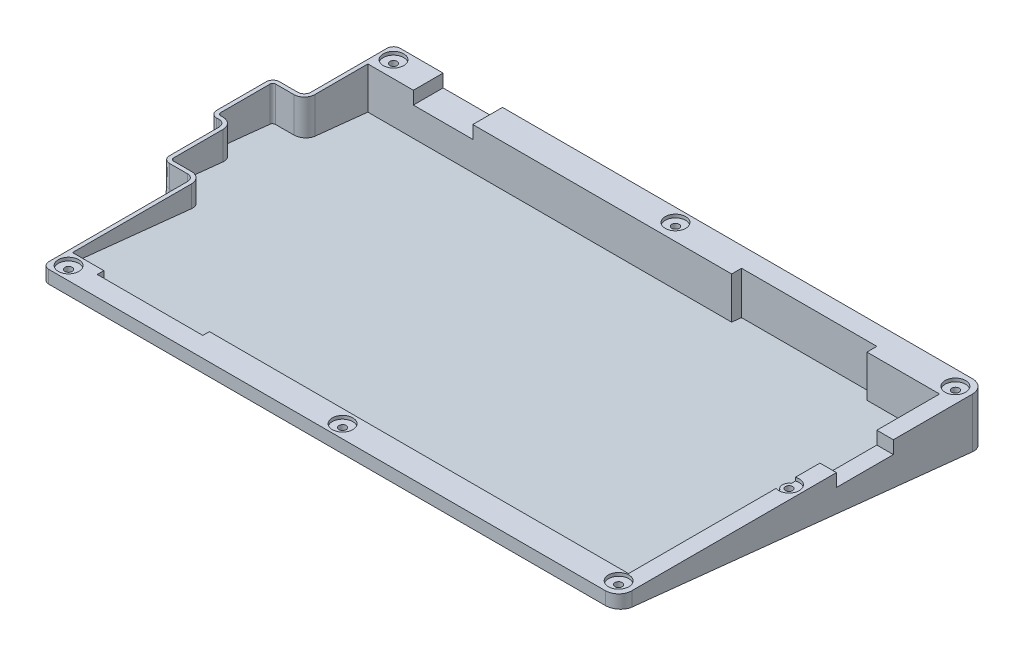
SolidWorks part; units mm, degrees
ref_plane "Front Plane" through (0, 0, 0) normal (0, 0, 1) x (1, 0, 0)
ref_plane "Top Plane" through (0, 0, 0) normal (0, 1, 0) x (1, 0, 0)
ref_plane "Right Plane" through (0, 0, 0) normal (1, 0, 0) x (0, 0, -1)
sketch "Sketch1" plane through (0, 0, 0) normal (0, 1, 0) x (1, 0, 0)
  line L0 (138.4196, 31.7518) -> (125.4196, 31.7518)
  line L1 (-35.0204, 31.7518) -> (107.4196, 31.7518)
  line L2 (140.4196, 29.7518) -> (140.4196, 6.7018)
  line L3 (-34.0204, 3.7518) -> (-34.0204, 22.7518)
  line L4 (136.4596, 27.7518) -> (136.4396, 27.7518)
  line L5 (142.4196, 4.7018) -> (147.9496, 4.7018)
  line L6 (-34.0204, 22.7518) -> (-12.0204, 22.7518)
  line L8 (149.9496, 2.7018) -> (149.9496, -12.3482)
  line L11 (147.9496, -14.3482) -> (147.1896, -14.3482)
  line L14 (145.1896, -16.3482) -> (145.1896, -31.3982)
  line L17 (143.1896, -33.3982) -> (137.6696, -33.3982)
  line L20 (135.6696, -35.3982) -> (135.6696, -77.4982)
  line L21 (-34.0204, -25.6003) -> (-34.0204, -71.4982)
  line L23 (133.6696, -79.4982) -> (-35.0204, -79.4982)
  line L28 (-39.0204, 27.7518) -> (-39.0204, 3.7518)
  line L31 (-34.0204, 3.7518) -> (-39.0204, 3.7518)
  line L32 (-34.0204, -13.4982) -> (-39.0204, -13.4982)
  line L33 (-39.0204, -75.4982) -> (-39.0204, -13.4982)
  line L34 (-34.0204, -71.4982) -> (92.9796, -71.4982)
  line L35 (92.9796, -71.4982) -> (92.9796, -73.4982)
  line L36 (92.9796, -73.4982) -> (124.9796, -73.4982)
  line L37 (124.9796, -73.4982) -> (124.9796, -71.4982)
  line L39 (134.4706, -35.3982) -> (134.4706, -71.4982)
  line L40 (134.4706, -71.4982) -> (124.9796, -71.4982)
  line L41 (137.6696, -32.1992) -> (143.1896, -32.1992)
  line L42 (-34.0204, -13.4982) -> (-34.0204, -22.1362)
  line L43 (143.9906, -31.3982) -> (143.9906, -16.3482)
  line L44 (-12.0204, 22.7518) -> (-12.0204, 25.7518)
  line L45 (147.1896, -13.1492) -> (147.9496, -13.1492)
  line L46 (148.7506, -12.3482) -> (148.7506, 2.7018)
  line L47 (-12.0204, 25.7518) -> (28.9796, 25.7518)
  line L48 (28.9796, 25.7518) -> (28.9796, 22.7518)
  line L49 (28.9796, 22.7518) -> (107.4196, 22.7518)
  line L50 (147.9496, 3.5027) -> (142.4196, 3.5027)
  line L51 (107.4196, 22.7518) -> (107.4196, 31.7518)
  line L52 (139.2206, 6.7018) -> (139.2206, 22.7518)
  line L53 (125.4196, 31.7518) -> (125.4196, 22.7518)
  line L54 (139.2206, 22.7518) -> (125.4196, 22.7518)
  arc A0 (138.4196, 31.7518) -> (140.4196, 29.7518) centre (138.4196, 29.7518) cw
  arc A1 (140.4196, 6.7018) -> (142.4196, 4.7018) centre (142.4196, 6.7018) ccw
  arc A2 (149.9496, 2.7018) -> (147.9496, 4.7018) centre (147.9496, 2.7018) ccw
  arc A3 (149.9496, -12.3482) -> (147.9496, -14.3482) centre (147.9496, -12.3482) cw
  arc A4 (147.1896, -14.3482) -> (145.1896, -16.3482) centre (147.1896, -16.3482) ccw
  arc A5 (145.1896, -31.3982) -> (143.1896, -33.3982) centre (143.1896, -31.3982) cw
  arc A6 (-35.0204, 31.7518) -> (-39.0204, 27.7518) centre (-35.0204, 27.7518) ccw
  arc A7 (-39.0204, -75.4982) -> (-35.0204, -79.4982) centre (-35.0204, -75.4982) ccw
  arc A8 (133.6696, -79.4982) -> (135.6696, -77.4982) centre (133.6696, -77.4982) ccw
  arc A9 (135.6696, -35.3982) -> (137.6696, -33.3982) centre (137.6696, -35.3982) cw
  circle A10 centre (-34.4204, 27.1518) radius 1.1
  circle A11 centre (51.0096, 27.7518) radius 1.1
  circle A12 centre (136.4396, 27.7518) radius 1.1
  circle A13 centre (-34.4204, -74.8982) radius 1.1
  circle A14 centre (48.6296, -75.4982) radius 1.1
  circle A15 centre (131.6496, -75.4982) radius 1.1
  circle A16 centre (-35.0204, -23.8682) radius 1.1
  arc A27 (-34.0204, -22.1362) -> (-34.0204, -25.6003) centre (-35.0204, -23.8682) cw
  arc A28 (139.2206, 6.7018) -> (142.4196, 3.5027) centre (142.4196, 6.7018) ccw
  arc A29 (147.9496, 3.5027) -> (148.7506, 2.7018) centre (147.9496, 2.7018) cw
  arc A30 (148.7506, -12.3482) -> (147.9496, -13.1492) centre (147.9496, -12.3482) cw
  arc A31 (147.1896, -13.1492) -> (143.9906, -16.3482) centre (147.1896, -16.3482) ccw
  arc A32 (143.9906, -31.3982) -> (143.1896, -32.1992) centre (143.1896, -31.3982) cw
  arc A33 (137.6696, -32.1992) -> (134.4706, -35.3982) centre (137.6696, -35.3982) ccw
extrude "Boss-Extrude2" add sketch "Sketch1" against normal blind 4.7 contours L41 A33 L39 L40 L37 L36 L35 L34 L21 A27 L42 L32 L33 A7 L23 A8 L20 A9 L17 A5 L14 A4 L11 A3 L8 A2 L5 A1 L2 A0 L0 L53 L54 L52 A28 L50 A29 L46 A30 L45 A31 L43 A32 A12 A13 A14 A15 | L1 A6 L28 L31 L3 L6 L44 L47 L48 L49 L51 A11 A10 region at (138.2833, 0, -29.6154) region at (31.7683, 0, -26.4895)
move or copy body "Body-Move/Copy1" bodies to move or copy 105 104 copy no rotation origin (55.4646, -2.35, 0) rotation axis (0, 0, 1) rotation angle 180
sketch "Sketch3" plane through (149.9496, 0, 0) normal (1, 0, 0) x (0, 0, -1)
  line L0 (-79.4982, 0) -> (-79.4982, -4.7) construction
  line L1 (-79.4982, 0) -> (-79.4982, -4.7)
  line L2 (31.7518, 0) -> (31.7518, -4.7) construction
  line L3 (31.7518, 0) -> (31.7518, -4.7)
  line L5 (-79.4982, -4.7) -> (31.7518, -16.3928)
  line L6 (31.7518, -16.3928) -> (31.7518, -4.7)
  line L7 (31.7518, -4.7) -> (-79.4982, -4.7)
  line M3 (-75.4982, -4.7) -> (-13.4982, -4.7)
  dimension "D1" = 6
extrude "Boss-Extrude3" add sketch "Sketch3" against normal up to surface (188.97 mm away) contours L6 L7 L5 M3 region at (149.9496, -8.5976, 5.3315) up to face at (-39.0204, -2.35, 4.8232)
sketch "Sketch4" plane through (0, -4.7, 0) normal (0, 1, 0) x (1, 0, 0)
  line L2 (145.9496, -79.4982) -> (149.9496, -79.4982)
  line L3 (149.9496, -79.4982) -> (149.9496, -75.4982)
  line L4 (-29.4904, 6.7018) -> (-29.4904, 29.7518)
  line L5 (-27.4904, 31.7518) -> (-39.0204, 31.7518)
  line L6 (-36.2604, -14.3482) -> (-37.0204, -14.3482)
  line L7 (-39.0204, -12.3482) -> (-39.0204, -79.4982)
  line L8 (-39.0204, -79.4982) -> (-22.7404, -79.4982)
  line L9 (-24.7404, -77.4982) -> (-24.7404, -35.3982)
  line L10 (-26.7404, -33.3982) -> (-32.2604, -33.3982)
  line L11 (-34.2604, -31.3982) -> (-34.2604, -16.3482)
  line L12 (-36.2604, -14.3482) -> (-37.0204, -14.3482)
  line L13 (-39.0204, -12.3482) -> (-39.0204, -79.4982)
  line L14 (-39.0204, -79.4982) -> (-22.7404, -79.4982)
  line L15 (-24.7404, -77.4982) -> (-24.7404, -35.3982)
  line L16 (-26.7404, -33.3982) -> (-32.2604, -33.3982)
  line L17 (-34.2604, -31.3982) -> (-34.2604, -16.3482)
  line L18 (-39.0204, 31.7518) -> (-39.0204, 2.7018)
  line L19 (-37.0204, 4.7018) -> (-31.4904, 4.7018)
  line L20 (-29.4904, 6.7018) -> (-29.4904, 29.7518)
  line L21 (-27.4904, 31.7518) -> (-39.0204, 31.7518)
  line L22 (-39.0204, 31.7518) -> (-39.0204, 2.7018)
  line L23 (-37.0204, 4.7018) -> (-31.4904, 4.7018)
  line L24 (145.9496, -79.4982) -> (149.9496, -79.4982)
  line L25 (149.9496, -79.4982) -> (149.9496, -75.4982)
  line L26 (149.9496, 31.7518) -> (145.9496, 31.7518)
  line L27 (149.9496, 27.7518) -> (149.9496, 31.7518)
  line L28 (149.9496, 31.7518) -> (145.9496, 31.7518)
  line L29 (149.9496, 27.7518) -> (149.9496, 31.7518)
  arc A1 (145.9496, -79.4982) -> (149.9496, -75.4982) centre (145.9496, -75.4982) ccw
  arc A2 (145.9496, -79.4982) -> (149.9496, -75.4982) centre (145.9496, -75.4982) ccw
  arc A3 (-27.4904, 31.7518) -> (-29.4904, 29.7518) centre (-27.4904, 29.7518) ccw
  arc A4 (-37.0204, 4.7018) -> (-39.0204, 2.7018) centre (-37.0204, 2.7018) ccw
  arc A5 (-39.0204, -12.3482) -> (-37.0204, -14.3482) centre (-37.0204, -12.3482) ccw
  arc A6 (-24.7404, -77.4982) -> (-22.7404, -79.4982) centre (-22.7404, -77.4982) ccw
  arc A7 (-24.7404, -35.3982) -> (-26.7404, -33.3982) centre (-26.7404, -35.3982) ccw
  arc A8 (-34.2604, -31.3982) -> (-32.2604, -33.3982) centre (-32.2604, -31.3982) ccw
  arc A9 (-34.2604, -16.3482) -> (-36.2604, -14.3482) centre (-36.2604, -16.3482) ccw
  arc A10 (-39.0204, -12.3482) -> (-37.0204, -14.3482) centre (-37.0204, -12.3482) ccw
  arc A11 (-24.7404, -77.4982) -> (-22.7404, -79.4982) centre (-22.7404, -77.4982) ccw
  arc A12 (-24.7404, -35.3982) -> (-26.7404, -33.3982) centre (-26.7404, -35.3982) ccw
  arc A13 (-34.2604, -31.3982) -> (-32.2604, -33.3982) centre (-32.2604, -31.3982) ccw
  arc A14 (-34.2604, -16.3482) -> (-36.2604, -14.3482) centre (-36.2604, -16.3482) ccw
  arc A15 (-31.4904, 4.7018) -> (-29.4904, 6.7018) centre (-31.4904, 6.7018) ccw
  arc A16 (-27.4904, 31.7518) -> (-29.4904, 29.7518) centre (-27.4904, 29.7518) ccw
  arc A17 (-37.0204, 4.7018) -> (-39.0204, 2.7018) centre (-37.0204, 2.7018) ccw
  arc A18 (-31.4904, 4.7018) -> (-29.4904, 6.7018) centre (-31.4904, 6.7018) ccw
  arc A19 (149.9496, 27.7518) -> (145.9496, 31.7518) centre (145.9496, 27.7518) ccw
  arc A20 (149.9496, 27.7518) -> (145.9496, 31.7518) centre (145.9496, 27.7518) ccw
  dimension "D1" = 0
  dimension "D2" = 0
  dimension "D3" = 0
  dimension "D4" = 0
extrude "Cut-Extrude1" cut sketch "Sketch4" against normal through all
ref_plane "Plane4" through (0, 15, 0) normal (0, 1, 0) x (1, 0, 0)
sketch "Sketch10" plane through (0, 15, 0) normal (0, 1, 0) x (1, 0, 0)
  line L0 (-14.4904, 22.7518) -> (3.5096, 22.7518)
  line L1 (144.9496, 3.7518) -> (144.9496, -13.4982)
  line L27 (-14.4904, 31.7518) -> (-14.4904, 22.7518)
  line L28 (-14.4904, 22.7518) -> (-28.2913, 22.7518)
  line L29 (-28.2913, 22.7518) -> (-28.2913, 6.7018)
  line L30 (-31.4904, 3.5027) -> (-37.0204, 3.5027)
  line L31 (-37.8213, 2.7018) -> (-37.8213, -12.3482)
  line L32 (-37.0204, -13.1492) -> (-36.2604, -13.1492)
  line L33 (-33.0613, -16.3482) -> (-33.0613, -31.3982)
  line L34 (-32.2604, -32.1992) -> (-26.7404, -32.1992)
  line L35 (-23.5413, -35.3982) -> (-23.5413, -71.4982)
  line L36 (-23.5413, -71.4982) -> (-14.0504, -71.4982)
  line L37 (-14.0504, -71.4982) -> (-14.0504, -73.4982)
  line L38 (-14.0504, -73.4982) -> (17.9496, -73.4982)
  line L39 (17.9496, -73.4982) -> (17.9496, -71.4982)
  line L40 (17.9496, -71.4982) -> (144.9496, -71.4982)
  line L41 (144.9496, -71.4982) -> (144.9496, -25.6003)
  line L42 (144.9496, -22.1362) -> (144.9496, -13.4982)
  line L43 (144.9496, -13.4982) -> (149.9496, -13.4982)
  line L44 (149.9496, -13.4982) -> (149.9496, 3.7518)
  line L45 (149.9496, 3.7518) -> (144.9496, 3.7518)
  line L46 (144.9496, 3.7518) -> (144.9496, 22.7518)
  line L47 (144.9496, 22.7518) -> (122.9496, 22.7518)
  line L48 (122.9496, 22.7518) -> (122.9496, 25.7518)
  line L49 (122.9496, 25.7518) -> (81.9496, 25.7518)
  line L50 (81.9496, 25.7518) -> (81.9496, 22.7518)
  line L51 (81.9496, 22.7518) -> (3.5096, 22.7518)
  line L52 (3.5096, 22.7518) -> (3.5096, 31.7518)
  line L53 (3.5096, 31.7518) -> (-14.4904, 31.7518)
  line L54 (-14.4904, 31.7518) -> (-14.4904, 22.7518)
  line L55 (-14.4904, 22.7518) -> (-28.2913, 22.7518)
  line L56 (-28.2913, 22.7518) -> (-28.2913, 6.7018)
  line L57 (-31.4904, 3.5027) -> (-37.0204, 3.5027)
  line L58 (-37.8213, 2.7018) -> (-37.8213, -12.3482)
  line L59 (-37.0204, -13.1492) -> (-36.2604, -13.1492)
  line L60 (-33.0613, -16.3482) -> (-33.0613, -31.3982)
  line L61 (-32.2604, -32.1992) -> (-26.7404, -32.1992)
  line L62 (-23.5413, -35.3982) -> (-23.5413, -71.4982)
  line L63 (-23.5413, -71.4982) -> (-14.0504, -71.4982)
  line L64 (-14.0504, -71.4982) -> (-14.0504, -73.4982)
  line L65 (-14.0504, -73.4982) -> (17.9496, -73.4982)
  line L66 (17.9496, -73.4982) -> (17.9496, -71.4982)
  line L67 (17.9496, -71.4982) -> (144.9496, -71.4982)
  line L68 (144.9496, -71.4982) -> (144.9496, -25.6003)
  line L69 (144.9496, -22.1362) -> (144.9496, -13.4982)
  line L70 (144.9496, -13.4982) -> (149.9496, -13.4982)
  line L71 (149.9496, -13.4982) -> (149.9496, 3.7518)
  line L72 (149.9496, 3.7518) -> (144.9496, 3.7518)
  line L73 (144.9496, 3.7518) -> (144.9496, 22.7518)
  line L74 (144.9496, 22.7518) -> (122.9496, 22.7518)
  line L75 (122.9496, 22.7518) -> (122.9496, 25.7518)
  line L76 (122.9496, 25.7518) -> (81.9496, 25.7518)
  line L77 (81.9496, 25.7518) -> (81.9496, 22.7518)
  line L78 (81.9496, 22.7518) -> (3.5096, 22.7518)
  line L79 (3.5096, 22.7518) -> (3.5096, 31.7518)
  line L80 (3.5096, 31.7518) -> (-14.4904, 31.7518)
  arc A7 (-31.4904, 3.5027) -> (-28.2913, 6.7018) centre (-31.4904, 6.7018) ccw
  arc A8 (-37.0204, 3.5027) -> (-37.8213, 2.7018) centre (-37.0204, 2.7018) ccw
  arc A9 (-37.8213, -12.3482) -> (-37.0204, -13.1492) centre (-37.0204, -12.3482) ccw
  arc A10 (-33.0613, -16.3482) -> (-36.2604, -13.1492) centre (-36.2604, -16.3482) ccw
  arc A11 (-33.0613, -31.3982) -> (-32.2604, -32.1992) centre (-32.2604, -31.3982) ccw
  arc A12 (-23.5413, -35.3982) -> (-26.7404, -32.1992) centre (-26.7404, -35.3982) ccw
  arc A13 (144.9496, -22.1362) -> (144.9496, -25.6003) centre (145.9496, -23.8682) ccw
  arc A14 (-31.4904, 3.5027) -> (-28.2913, 6.7018) centre (-31.4904, 6.7018) ccw
  arc A15 (-37.0204, 3.5027) -> (-37.8213, 2.7018) centre (-37.0204, 2.7018) ccw
  arc A16 (-37.8213, -12.3482) -> (-37.0204, -13.1492) centre (-37.0204, -12.3482) ccw
  arc A17 (-33.0613, -16.3482) -> (-36.2604, -13.1492) centre (-36.2604, -16.3482) ccw
  arc A18 (-33.0613, -31.3982) -> (-32.2604, -32.1992) centre (-32.2604, -31.3982) ccw
  arc A19 (-23.5413, -35.3982) -> (-26.7404, -32.1992) centre (-26.7404, -35.3982) ccw
  arc A20 (144.9496, -22.1362) -> (144.9496, -25.6003) centre (145.9496, -23.8682) ccw
  dimension "D1" = 0
extrude "Cut-Extrude2" cut sketch "Sketch10" against normal through all contours A20 L69 L1 L73 L74 L75 L76 L77 L78 L0 L55 L56 A14 L57 A15 L58 A16 L59 A17 L60 A18 L61 A19 L62 L63 L64 L65 L66 L67 L68 region at (57.9798, 15, 23.6888)
sketch "Sketch11" plane through (144.9496, 0, 0) normal (-1, 0, 0) x (0, 0, 1)
  line L0 (-22.7518, -15.4469) -> (71.4982, -5.5408)
  line L1 (71.4982, -5.5408) -> (71.4982, -3.5408)
  line L2 (71.4982, 0) -> (71.4982, -5.5408) construction
  line L3 (71.4982, -3.5408) -> (-22.7518, -13.4469)
  line L4 (-22.7518, 0) -> (-22.7518, -15.4469) construction
  line L5 (-22.7518, -13.4469) -> (-22.7518, -15.4469)
  dimension "D1" = 2
  dimension "D2" = 2
extrude "Boss-Extrude4" add sketch "Sketch11" along normal up to surface (182.7709 mm away)
sketch "Sketch12" plane through (0, -10.9348, 1.1493) normal (0, 0.9945, -0.1045) x (1, 0, 0)
  line L0 (-29.4904, 7.8943) -> (-29.4904, 24.0327) construction
  line L1 (-29.4904, 24.0327) -> (-37.8213, 24.0327) construction
  line L2 (-37.8213, 24.0327) -> (-37.8213, 5.715) construction
  line L3 (-37.0204, 5.8833) -> (-31.4904, 5.8833) construction
  line L4 (-36.2604, -13.2716) -> (-37.0204, -13.2716) construction
  line L5 (-37.8213, -13.1033) -> (-37.8213, -70.7364) construction
  line L6 (-37.8213, -70.7364) -> (-24.7404, -70.7364) construction
  line L7 (-24.7404, -70.7364) -> (-24.7404, -34.4376) construction
  line L8 (-26.7404, -32.4266) -> (-32.2604, -32.4266) construction
  line L9 (-34.2604, -30.4155) -> (-34.2604, -15.2826) construction
  line L10 (-29.4904, 7.8943) -> (-29.4904, 24.0327)
  line L11 (-29.4904, 24.0327) -> (-37.8213, 24.0327)
  line L12 (-37.8213, 24.0327) -> (-37.8213, 5.715)
  line L13 (-37.0204, 5.8833) -> (-31.4904, 5.8833)
  line L14 (-36.2604, -13.2716) -> (-37.0204, -13.2716)
  line L15 (-37.8213, -13.1033) -> (-37.8213, -70.7364)
  line L16 (-37.8213, -70.7364) -> (-24.7404, -70.7364)
  line L17 (-24.7404, -70.7364) -> (-24.7404, -34.4376)
  line L18 (-26.7404, -32.4266) -> (-32.2604, -32.4266)
  line L19 (-34.2604, -30.4155) -> (-34.2604, -15.2826)
  line L20 (-37.8213, 24.0327) -> (-37.8213, 25.9101)
  line L21 (-29.4904, 24.0327) -> (-29.4904, 27.1127)
  line L22 (-29.4904, 27.1127) -> (-37.8213, 25.9101)
  ellipse E0 centre (-31.4904, 7.8943) end of major axis (-31.4904, 9.9053) minor radius 2 (-31.4904, 5.8833) -> (-29.4904, 7.8943) ccw construction
  ellipse E1 centre (-37.0204, 3.8723) end of major axis (-37.0204, 5.8833) minor radius 2 (-37.0204, 5.8833) -> (-37.8213, 5.715) ccw construction
  ellipse E2 centre (-37.0204, -11.2606) end of major axis (-37.0204, -9.2496) minor radius 2 (-37.8213, -13.1033) -> (-37.0204, -13.2716) ccw construction
  ellipse E3 centre (-26.7404, -34.4376) end of major axis (-26.7404, -32.4266) minor radius 2 (-24.7404, -34.4376) -> (-26.7404, -32.4266) ccw construction
  ellipse E4 centre (-32.2604, -30.4155) end of major axis (-32.2604, -28.4045) minor radius 2 (-34.2604, -30.4155) -> (-32.2604, -32.4266) ccw construction
  ellipse E5 centre (-36.2604, -15.2826) end of major axis (-36.2604, -13.2716) minor radius 2 (-34.2604, -15.2826) -> (-36.2604, -13.2716) ccw construction
  ellipse E6 centre (-31.4904, 7.8943) end of major axis (-31.4904, 9.9053) minor radius 2 (-31.4904, 5.8833) -> (-29.4904, 7.8943) ccw
  ellipse E7 centre (-37.0204, 3.8723) end of major axis (-37.0204, 5.8833) minor radius 2 (-37.0204, 5.8833) -> (-37.8213, 5.715) ccw
  ellipse E8 centre (-37.0204, -11.2606) end of major axis (-37.0204, -9.2496) minor radius 2 (-37.8213, -13.1033) -> (-37.0204, -13.2716) ccw
  ellipse E9 centre (-26.7404, -34.4376) end of major axis (-26.7404, -32.4266) minor radius 2 (-24.7404, -34.4376) -> (-26.7404, -32.4266) ccw
  ellipse E10 centre (-32.2604, -30.4155) end of major axis (-32.2604, -28.4045) minor radius 2 (-34.2604, -30.4155) -> (-32.2604, -32.4266) ccw
  ellipse E11 centre (-36.2604, -15.2826) end of major axis (-36.2604, -13.2716) minor radius 2 (-34.2604, -15.2826) -> (-36.2604, -13.2716) ccw
sketch "Sketch26" plane through (-37.8213, 0, 0) normal (-1, 0, 0) x (0, 0, 1)
  line L0 (14.1808, -9.5651) -> (-4.5344, -11.5322)
  line L1 (-4.5344, -13.5322) -> (14.1808, -11.5651)
  line L4 (-22.7518, -15.4469) -> (-4.5344, -13.5322)
  line L5 (-4.5344, -13.5322) -> (-4.5344, -11.5322)
  line L6 (-4.5344, -11.5322) -> (-22.7518, -13.4469)
  line L7 (-22.7518, -13.4469) -> (-22.7518, -15.4469)
  line L8 (-22.7518, -15.4469) -> (-4.5344, -13.5322)
  line L9 (-4.5344, -13.5322) -> (-4.5344, -11.5322)
  line L10 (-4.5344, -11.5322) -> (-22.7518, -13.4469)
  line L11 (-22.7518, -13.4469) -> (-22.7518, -15.4469)
  line L12 (14.1808, -9.5651) -> (14.1808, -11.5651)
  line L13 (14.1808, -11.5651) -> (71.4982, -5.5408)
  line L14 (71.4982, -5.5408) -> (71.4982, -3.5408)
  line L15 (71.4982, -3.5408) -> (14.1808, -9.5651)
  line L16 (14.1808, -9.5651) -> (14.1808, -11.5651)
  line L17 (14.1808, -11.5651) -> (71.4982, -5.5408)
  line L18 (71.4982, -5.5408) -> (71.4982, -3.5408)
  line L19 (71.4982, -3.5408) -> (14.1808, -9.5651)
  line M9 (14.1808, -9.5651) -> (14.1808, -11.5651)
  line M10 (14.1808, -11.5651) -> (71.4982, -5.5408)
  line M11 (71.4982, -5.5408) -> (71.4982, -3.5408)
  line M12 (71.4982, -3.5408) -> (14.1808, -9.5651)
  dimension "D1" = 0
  dimension "D2" = 0
extrude "Boss-Extrude10" add sketch "Sketch26" along normal blind 11 contours L10 L11 L8 L9 | L9 L1 L0 M9 | M12 M9 M10 M11 region at (-37.8213, -11.5487, 4.8232) region at (-37.8213, -7.553, 42.8395) region at (-37.8213, -13.4895, -13.6431)
sketch "Sketch28" plane through (0, -10.9348, 1.1493) normal (0, 0.9945, -0.1045) x (1, 0, 0)
  line L0 (-48.8213, 24.0327) -> (-52.7132, 28.3929)
  line L1 (-52.7132, 28.3929) -> (-29.4904, 30.8021)
  line L2 (-29.4904, 30.8021) -> (-29.4904, 24.0327)
  line L10 (-29.4904, 7.8943) -> (-29.4904, 24.0327)
  line L11 (-29.4904, 24.0327) -> (-48.8213, 24.0327)
  line L12 (-48.8213, 24.0327) -> (-48.8213, -70.7364)
  line L13 (-48.8213, -70.7364) -> (-24.7404, -70.7364)
  line L14 (-24.7404, -70.7364) -> (-24.7404, -34.4376)
  line L15 (-26.7404, -32.4266) -> (-32.2604, -32.4266)
  line L16 (-34.2604, -30.4155) -> (-34.2604, -15.2826)
  line L17 (-36.2604, -13.2716) -> (-37.0204, -13.2716)
  line L18 (-39.0204, -11.2606) -> (-39.0204, 3.8723)
  line L19 (-37.0204, 5.8833) -> (-31.4904, 5.8833)
  line L20 (-29.4904, 7.8943) -> (-29.4904, 24.0327)
  line L21 (-29.4904, 24.0327) -> (-48.8213, 24.0327)
  line L22 (-48.8213, 24.0327) -> (-48.8213, -70.7364)
  line L23 (-48.8213, -70.7364) -> (-24.7404, -70.7364)
  line L24 (-24.7404, -70.7364) -> (-24.7404, -34.4376)
  line L25 (-26.7404, -32.4266) -> (-32.2604, -32.4266)
  line L26 (-34.2604, -30.4155) -> (-34.2604, -15.2826)
  line L27 (-36.2604, -13.2716) -> (-37.0204, -13.2716)
  line L28 (-39.0204, -11.2606) -> (-39.0204, 3.8723)
  line L29 (-37.0204, 5.8833) -> (-31.4904, 5.8833)
  ellipse E6 centre (-31.4904, 7.8943) end of major axis (-31.4904, 9.9053) minor radius 2 (-31.4904, 5.8833) -> (-29.4904, 7.8943) ccw
  ellipse E7 centre (-26.7404, -34.4376) end of major axis (-26.7404, -32.4266) minor radius 2 (-24.7404, -34.4376) -> (-26.7404, -32.4266) ccw
  ellipse E8 centre (-32.2604, -30.4155) end of major axis (-32.2604, -28.4045) minor radius 2 (-34.2604, -30.4155) -> (-32.2604, -32.4266) ccw
  ellipse E9 centre (-36.2604, -15.2826) end of major axis (-36.2604, -13.2716) minor radius 2 (-34.2604, -15.2826) -> (-36.2604, -13.2716) ccw
  ellipse E10 centre (-37.0204, -11.2606) end of major axis (-37.0204, -9.2496) minor radius 2 (-39.0204, -11.2606) -> (-37.0204, -13.2716) ccw
  ellipse E11 centre (-37.0204, 3.8723) end of major axis (-37.0204, 5.8833) minor radius 2 (-37.0204, 5.8833) -> (-39.0204, 3.8723) ccw
  ellipse E12 centre (-31.4904, 7.8943) end of major axis (-31.4904, 9.9053) minor radius 2 (-31.4904, 5.8833) -> (-29.4904, 7.8943) ccw
  ellipse E13 centre (-26.7404, -34.4376) end of major axis (-26.7404, -32.4266) minor radius 2 (-24.7404, -34.4376) -> (-26.7404, -32.4266) ccw
  ellipse E14 centre (-32.2604, -30.4155) end of major axis (-32.2604, -28.4045) minor radius 2 (-34.2604, -30.4155) -> (-32.2604, -32.4266) ccw
  ellipse E15 centre (-36.2604, -15.2826) end of major axis (-36.2604, -13.2716) minor radius 2 (-34.2604, -15.2826) -> (-36.2604, -13.2716) ccw
  ellipse E16 centre (-37.0204, -11.2606) end of major axis (-37.0204, -9.2496) minor radius 2 (-39.0204, -11.2606) -> (-37.0204, -13.2716) ccw
  ellipse E17 centre (-37.0204, 3.8723) end of major axis (-37.0204, 5.8833) minor radius 2 (-37.0204, 5.8833) -> (-39.0204, 3.8723) ccw
  ellipse M17 centre (-31.4904, 7.8943) end of major axis (-31.4904, 9.9053) minor radius 2 (-31.4904, 5.8833) -> (-29.4904, 7.8943) ccw
  line M18 (-29.4904, 7.8943) -> (-29.4904, 24.0327)
  line M19 (-29.4904, 24.0327) -> (-48.8213, 24.0327)
  line M20 (-48.8213, 24.0327) -> (-48.8213, -70.7364)
  line M21 (-48.8213, -70.7364) -> (-24.7404, -70.7364)
  line M22 (-24.7404, -70.7364) -> (-24.7404, -34.4376)
  ellipse M23 centre (-26.7404, -34.4376) end of major axis (-26.7404, -32.4266) minor radius 2 (-24.7404, -34.4376) -> (-26.7404, -32.4266) ccw
  line M24 (-26.7404, -32.4266) -> (-32.2604, -32.4266)
  ellipse M25 centre (-32.2604, -30.4155) end of major axis (-32.2604, -28.4045) minor radius 2 (-32.2604, -32.4266) -> (-34.2604, -30.4155) cw
  line M26 (-34.2604, -30.4155) -> (-34.2604, -15.2826)
  ellipse M27 centre (-36.2604, -15.2826) end of major axis (-36.2604, -13.2716) minor radius 2 (-34.2604, -15.2826) -> (-36.2604, -13.2716) ccw
  line M28 (-36.2604, -13.2716) -> (-37.0204, -13.2716)
  ellipse M29 centre (-37.0204, -11.2606) end of major axis (-37.0204, -9.2496) minor radius 2 (-37.0204, -13.2716) -> (-39.0204, -11.2606) cw
  line M30 (-39.0204, -11.2606) -> (-39.0204, 3.8723)
  ellipse M31 centre (-37.0204, 3.8723) end of major axis (-37.0204, 5.8833) minor radius 2 (-39.0204, 3.8723) -> (-37.0204, 5.8833) cw
  line M32 (-37.0204, 5.8833) -> (-31.4904, 5.8833)
  dimension "D1" = 0
extrude "Cut-Extrude8" cut sketch "Sketch28" against normal blind 11 contours M32 M17 M18 M19 M20 M21 M22 M23 M24 M25 M26 M27 M28 M29 M30 M31 | L2 L1 L0 M19 region at (-39.4803, -13.7524, -25.6581) region at (-38.8035, -7.967, 29.3861)
sketch "Sketch30" plane through (122.9496, 0, 0) normal (-1, 0, 0) x (0, 0, 1)
  line L0 (-25.7518, -15.7622) -> (-22.7518, -15.4469)
  line L1 (-22.7518, -15.4469) -> (-22.7518, -13.4469)
  line L2 (-22.7518, -15.4469) -> (-22.7518, -13.4469) construction
  line L3 (-22.7518, -13.4469) -> (-25.7518, -13.7622)
  line L4 (-25.7518, 0) -> (-25.7518, -15.7622) construction
  line L5 (-25.7518, -13.7622) -> (-25.7518, -15.7622)
extrude "Boss-Extrude11" add sketch "Sketch30" along normal up to surface (41 mm away)
sketch "Sketch32" plane through (17.9496, 0, 0) normal (-1, 0, 0) x (0, 0, 1)
  line L0 (73.4982, -5.3306) -> (71.4982, -5.5408)
  line L1 (71.4982, -5.5408) -> (71.4982, -3.5408)
  line L2 (71.4982, -3.5408) -> (73.4982, -3.3306)
  line L3 (73.4982, 0) -> (73.4982, -5.3306) construction
  line L4 (73.4982, -3.3306) -> (73.4982, -5.3306)
  dimension "D1" = 2
extrude "Boss-Extrude14" add sketch "Sketch32" along normal up to surface (32 mm away)
sketch "Sketch35" plane through (0, 0, 0) normal (0, 1, 0) x (1, 0, 0)
  line L0 (149.9496, 3.7518) -> (149.9496, -13.4982)
  line L1 (149.9496, -13.4982) -> (144.9496, -13.4982)
  line L2 (144.9496, -13.4982) -> (144.9496, 3.7518)
  line L3 (144.9496, 3.7518) -> (149.9496, 3.7518)
ref_plane "Plane5" through (149.9496, -5.1204, 75.4982) normal (0, -1, 0) x (-1, 0, 0)
sketch "Sketch47" plane through (0, 0, 0) normal (0, 1, 0) x (1, 0, 0)
  circle A0 centre (145.3496, -74.8982) radius 3.1
  circle A1 centre (62.2996, -75.4982) radius 3.1
  circle A2 centre (-20.7204, -75.4982) radius 3.1
  circle A3 centre (-25.5104, 27.7518) radius 3.1
  circle A4 centre (59.9196, 27.7518) radius 3.1
  circle A5 centre (145.3496, 27.1518) radius 3.1
  circle A6 centre (145.9496, -23.8682) radius 3.1
extrude "Cut-Extrude17" cut sketch "Sketch47" against normal blind 1.8
sketch "Sketch48" plane through (0, 0, 0) normal (0, 1, 0) x (1, 0, 0)
  line L10 (145.9496, 31.7518) -> (3.5096, 31.7518)
  line L11 (3.5096, 31.7518) -> (3.5096, 22.7518)
  line L12 (3.5096, 22.7518) -> (81.9496, 22.7518)
  line L13 (81.9496, 22.7518) -> (81.9496, 25.7518)
  line L14 (81.9496, 25.7518) -> (122.9496, 25.7518)
  line L15 (122.9496, 25.7518) -> (122.9496, 22.7518)
  line L16 (122.9496, 22.7518) -> (144.9496, 22.7518)
  line L17 (144.9496, 22.7518) -> (144.9496, 3.7518)
  line L18 (144.9496, 3.7518) -> (149.9496, 3.7518)
  line L19 (149.9496, 3.7518) -> (149.9496, 27.7518)
  line L20 (145.9496, 31.7518) -> (3.5096, 31.7518)
  line L21 (3.5096, 31.7518) -> (3.5096, 22.7518)
  line L22 (3.5096, 22.7518) -> (81.9496, 22.7518)
  line L23 (81.9496, 22.7518) -> (81.9496, 25.7518)
  line L24 (81.9496, 25.7518) -> (122.9496, 25.7518)
  line L25 (122.9496, 25.7518) -> (122.9496, 22.7518)
  line L26 (122.9496, 22.7518) -> (144.9496, 22.7518)
  line L27 (144.9496, 22.7518) -> (144.9496, 3.7518)
  line L28 (144.9496, 3.7518) -> (149.9496, 3.7518)
  line L29 (149.9496, 3.7518) -> (149.9496, 27.7518)
  line L47 (144.9496, -13.4982) -> (144.9496, -20.9339)
  line L48 (144.9496, -26.8025) -> (144.9496, -71.4982)
  line L49 (144.9496, -71.4982) -> (17.9496, -71.4982)
  line L50 (17.9496, -71.4982) -> (17.9496, -73.4982)
  line L51 (17.9496, -73.4982) -> (-14.0504, -73.4982)
  line L52 (-14.0504, -73.4982) -> (-14.0504, -71.4982)
  line L53 (-14.0504, -71.4982) -> (-23.5413, -71.4982)
  line L54 (-23.5413, -71.4982) -> (-23.5413, -35.3982)
  line L55 (-26.7404, -32.1992) -> (-32.2604, -32.1992)
  line L56 (-33.0613, -31.3982) -> (-33.0613, -16.3482)
  line L57 (-36.2604, -13.1492) -> (-37.0204, -13.1492)
  line L58 (-37.8213, -12.3482) -> (-37.8213, 2.7018)
  line L59 (-37.0204, 3.5027) -> (-31.4904, 3.5027)
  line L60 (-28.2913, 6.7018) -> (-28.2913, 22.7518)
  line L61 (-28.2913, 22.7518) -> (-14.4904, 22.7518)
  line L62 (-14.4904, 22.7518) -> (-14.4904, 31.7518)
  line L63 (-14.4904, 31.7518) -> (-27.4904, 31.7518)
  line L64 (-29.4904, 29.7518) -> (-29.4904, 6.7018)
  line L65 (-31.4904, 4.7018) -> (-37.0204, 4.7018)
  line L66 (-39.0204, 2.7018) -> (-39.0204, -12.3482)
  line L67 (-37.0204, -14.3482) -> (-36.2604, -14.3482)
  line L68 (-34.2604, -16.3482) -> (-34.2604, -31.3982)
  line L69 (-32.2604, -33.3982) -> (-26.7404, -33.3982)
  line L70 (-24.7404, -35.3982) -> (-24.7404, -77.4982)
  line L71 (-22.7404, -79.4982) -> (145.9496, -79.4982)
  line L72 (149.9496, -75.4982) -> (149.9496, -13.4982)
  line L73 (149.9496, -13.4982) -> (144.9496, -13.4982)
  line L74 (144.9496, -13.4982) -> (144.9496, -20.9339)
  line L75 (144.9496, -26.8025) -> (144.9496, -71.4982)
  line L76 (144.9496, -71.4982) -> (17.9496, -71.4982)
  line L77 (17.9496, -71.4982) -> (17.9496, -73.4982)
  line L78 (17.9496, -73.4982) -> (-14.0504, -73.4982)
  line L79 (-14.0504, -73.4982) -> (-14.0504, -71.4982)
  line L80 (-14.0504, -71.4982) -> (-23.5413, -71.4982)
  line L81 (-23.5413, -71.4982) -> (-23.5413, -35.3982)
  line L82 (-26.7404, -32.1992) -> (-32.2604, -32.1992)
  line L83 (-33.0613, -31.3982) -> (-33.0613, -16.3482)
  line L84 (-36.2604, -13.1492) -> (-37.0204, -13.1492)
  line L85 (-37.8213, -12.3482) -> (-37.8213, 2.7018)
  line L86 (-37.0204, 3.5027) -> (-31.4904, 3.5027)
  line L87 (-28.2913, 6.7018) -> (-28.2913, 22.7518)
  line L88 (-28.2913, 22.7518) -> (-14.4904, 22.7518)
  line L89 (-14.4904, 22.7518) -> (-14.4904, 31.7518)
  line L90 (-14.4904, 31.7518) -> (-27.4904, 31.7518)
  line L91 (-29.4904, 29.7518) -> (-29.4904, 6.7018)
  line L92 (-31.4904, 4.7018) -> (-37.0204, 4.7018)
  line L93 (-39.0204, 2.7018) -> (-39.0204, -12.3482)
  line L94 (-37.0204, -14.3482) -> (-36.2604, -14.3482)
  line L95 (-34.2604, -16.3482) -> (-34.2604, -31.3982)
  line L96 (-32.2604, -33.3982) -> (-26.7404, -33.3982)
  line L97 (-24.7404, -35.3982) -> (-24.7404, -77.4982)
  line L98 (-22.7404, -79.4982) -> (145.9496, -79.4982)
  line L99 (149.9496, -75.4982) -> (149.9496, -13.4982)
  line L100 (149.9496, -13.4982) -> (144.9496, -13.4982)
  arc A1 (149.9496, 27.7518) -> (145.9496, 31.7518) centre (145.9496, 27.7518) ccw
  arc A2 (149.9496, 27.7518) -> (145.9496, 31.7518) centre (145.9496, 27.7518) ccw
  arc A18 (144.9496, -26.8025) -> (144.9496, -20.9339) centre (145.9496, -23.8682) ccw
  arc A19 (-23.5413, -35.3982) -> (-26.7404, -32.1992) centre (-26.7404, -35.3982) ccw
  arc A20 (-33.0613, -31.3982) -> (-32.2604, -32.1992) centre (-32.2604, -31.3982) ccw
  arc A21 (-33.0613, -16.3482) -> (-36.2604, -13.1492) centre (-36.2604, -16.3482) ccw
  arc A22 (-37.8213, -12.3482) -> (-37.0204, -13.1492) centre (-37.0204, -12.3482) ccw
  arc A23 (-37.0204, 3.5027) -> (-37.8213, 2.7018) centre (-37.0204, 2.7018) ccw
  arc A24 (-31.4904, 3.5027) -> (-28.2913, 6.7018) centre (-31.4904, 6.7018) ccw
  arc A25 (-27.4904, 31.7518) -> (-29.4904, 29.7518) centre (-27.4904, 29.7518) ccw
  arc A26 (-31.4904, 4.7018) -> (-29.4904, 6.7018) centre (-31.4904, 6.7018) ccw
  arc A27 (-37.0204, 4.7018) -> (-39.0204, 2.7018) centre (-37.0204, 2.7018) ccw
  arc A28 (-39.0204, -12.3482) -> (-37.0204, -14.3482) centre (-37.0204, -12.3482) ccw
  arc A29 (-34.2604, -16.3482) -> (-36.2604, -14.3482) centre (-36.2604, -16.3482) ccw
  arc A30 (-34.2604, -31.3982) -> (-32.2604, -33.3982) centre (-32.2604, -31.3982) ccw
  arc A31 (-24.7404, -35.3982) -> (-26.7404, -33.3982) centre (-26.7404, -35.3982) ccw
  arc A32 (-24.7404, -77.4982) -> (-22.7404, -79.4982) centre (-22.7404, -77.4982) ccw
  arc A33 (145.9496, -79.4982) -> (149.9496, -75.4982) centre (145.9496, -75.4982) ccw
  arc A34 (144.9496, -26.8025) -> (144.9496, -20.9339) centre (145.9496, -23.8682) ccw
  arc A35 (-23.5413, -35.3982) -> (-26.7404, -32.1992) centre (-26.7404, -35.3982) ccw
  arc A36 (-33.0613, -31.3982) -> (-32.2604, -32.1992) centre (-32.2604, -31.3982) ccw
  arc A37 (-33.0613, -16.3482) -> (-36.2604, -13.1492) centre (-36.2604, -16.3482) ccw
  arc A38 (-37.8213, -12.3482) -> (-37.0204, -13.1492) centre (-37.0204, -12.3482) ccw
  arc A39 (-37.0204, 3.5027) -> (-37.8213, 2.7018) centre (-37.0204, 2.7018) ccw
  arc A40 (-31.4904, 3.5027) -> (-28.2913, 6.7018) centre (-31.4904, 6.7018) ccw
  arc A41 (-27.4904, 31.7518) -> (-29.4904, 29.7518) centre (-27.4904, 29.7518) ccw
  arc A42 (-31.4904, 4.7018) -> (-29.4904, 6.7018) centre (-31.4904, 6.7018) ccw
  arc A43 (-37.0204, 4.7018) -> (-39.0204, 2.7018) centre (-37.0204, 2.7018) ccw
  arc A44 (-39.0204, -12.3482) -> (-37.0204, -14.3482) centre (-37.0204, -12.3482) ccw
  arc A45 (-34.2604, -16.3482) -> (-36.2604, -14.3482) centre (-36.2604, -16.3482) ccw
  arc A46 (-34.2604, -31.3982) -> (-32.2604, -33.3982) centre (-32.2604, -31.3982) ccw
  arc A47 (-24.7404, -35.3982) -> (-26.7404, -33.3982) centre (-26.7404, -35.3982) ccw
  arc A48 (-24.7404, -77.4982) -> (-22.7404, -79.4982) centre (-22.7404, -77.4982) ccw
  arc A49 (145.9496, -79.4982) -> (149.9496, -75.4982) centre (145.9496, -75.4982) ccw
  dimension "D1" = 0
  dimension "D2" = 0
extrude "Cut-Extrude18" cut sketch "Sketch48" against normal blind 0.8
